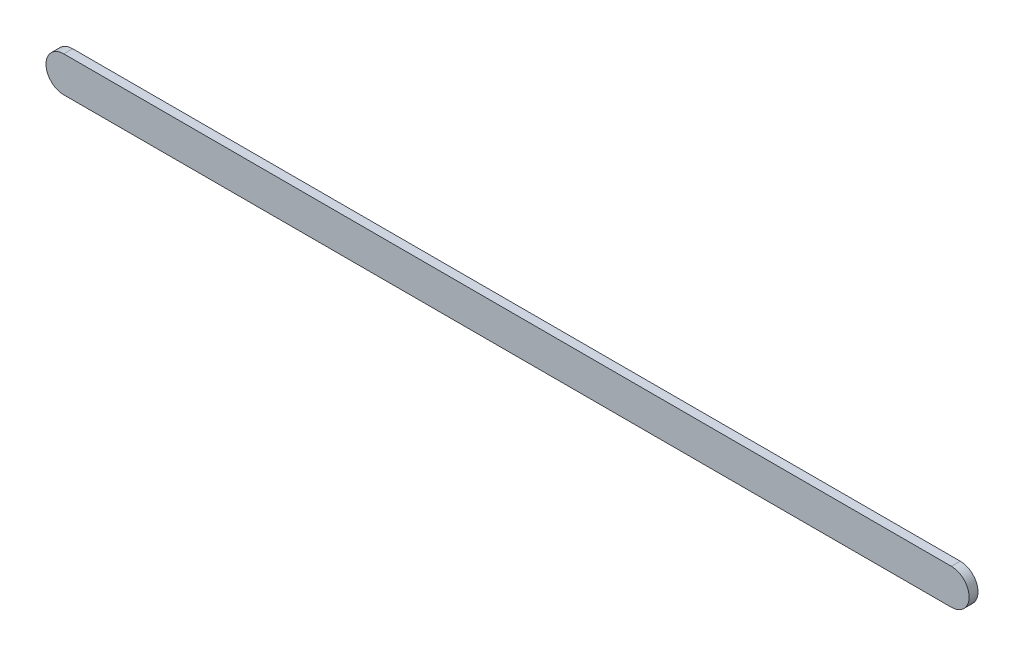
SolidWorks part; units mm, degrees
ref_plane "Front Plane" through (0, 0, 0) normal (0, 0, 1) x (1, 0, 0)
ref_plane "Top Plane" through (0, 0, 0) normal (0, 1, 0) x (1, 0, 0)
ref_plane "Right Plane" through (0, 0, 0) normal (1, 0, 0) x (0, 0, -1)
sketch "Sketch1" plane through (0, 0, 0) normal (0, 0, 1) x (1, 0, 0)
  line L0 (-53.3333, -5.1667) -> (196.6667, -5.1667) construction
  line L1 (-53.3333, -0.1667) -> (196.6667, -0.1667)
  line L2 (-53.3333, -10.1667) -> (196.6667, -10.1667)
  arc A0 (-53.3333, -0.1667) -> (-53.3333, -10.1667) centre (-53.3333, -5.1667) ccw
  arc A1 (196.6667, -10.1667) -> (196.6667, -0.1667) centre (196.6667, -5.1667) ccw
  point P2 (71.6667, -5.1667)
  dimension "D1" = 5
  dimension "D2" = 250
extrude "Boss-Extrude1" add sketch "Sketch1" along normal blind 2.5
ref_axis "Axis1" through (196.6667, -5.1667, 0) along (0, 0, 1)
ref_axis "Axis2" through (-53.3333, -5.1667, 0) along (0, 0, 1)
